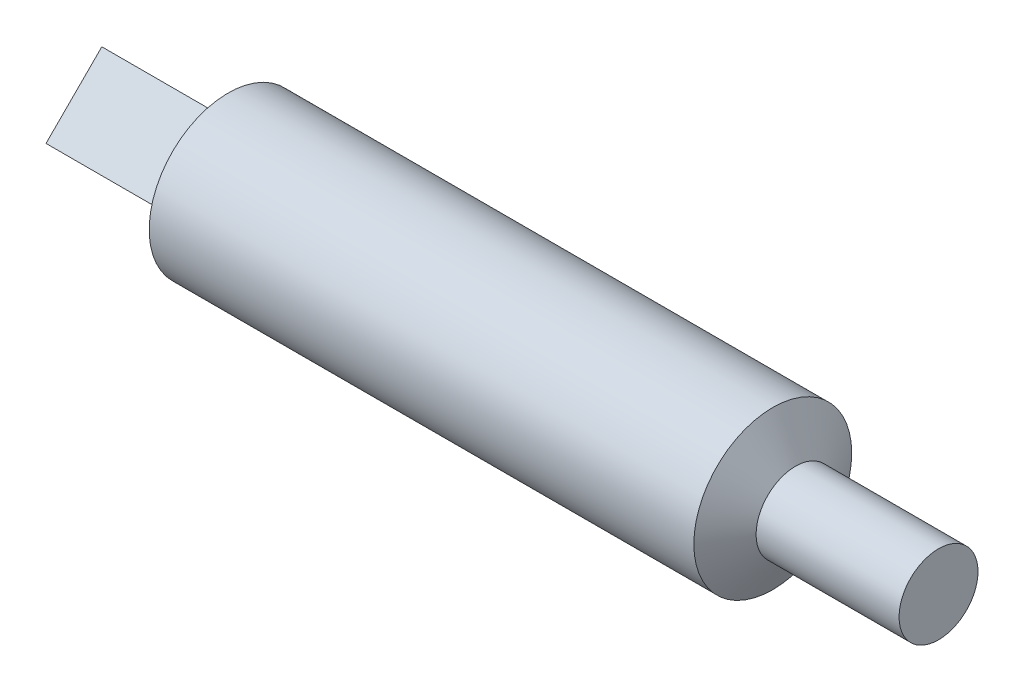
SolidWorks part; units mm, degrees
ref_plane "前视基准面" through (0, 0, 0) normal (0, 0, 1) x (1, 0, 0)
ref_plane "上视基准面" through (0, 0, 0) normal (0, 1, 0) x (1, 0, 0)
ref_plane "右视基准面" through (0, 0, 0) normal (1, 0, 0) x (0, 0, -1)
sketch "草图1" plane through (0, 0, 0) normal (1, 0, 0) x (0, 0, -1)
  circle A0 centre (0, 0) radius 5
  dimension "D1" = 10
extrude "凸台-拉伸1" add sketch "草图1" along normal blind 37
cosmetic thread "装饰螺纹线1" parameters "D2"=8.376
sketch "草图2" plane through (37, 0, 0) normal (1, 0, 0) x (0, 0, -1)
  circle A0 centre (0, 0) radius 2.5
  dimension "D1" = 5
extrude "凸台-拉伸2" add sketch "草图2" along normal blind 8
sketch "草图3" plane through (0, 0, 0) normal (-1, 0, 0) x (0, 0, 1)
  line L1 (0, 3.5355) -> (-3.5355, 0)
  line L2 (-3.5355, 0) -> (0, -3.5355)
  line L3 (0, -3.5355) -> (3.5355, 0)
  line L4 (3.5355, 0) -> (0, 3.5355)
  circle A0 centre (0, 0) radius 2.5 construction
  point P1 (0, 0)
  dimension "D1" = 5
extrude "凸台-拉伸3" add sketch "草图3" along normal blind 8
chamfer "倒角1" distance 2.5 angle 60 1 edges at (37, 0, -5) first distance on face at (37, 0, -5)
